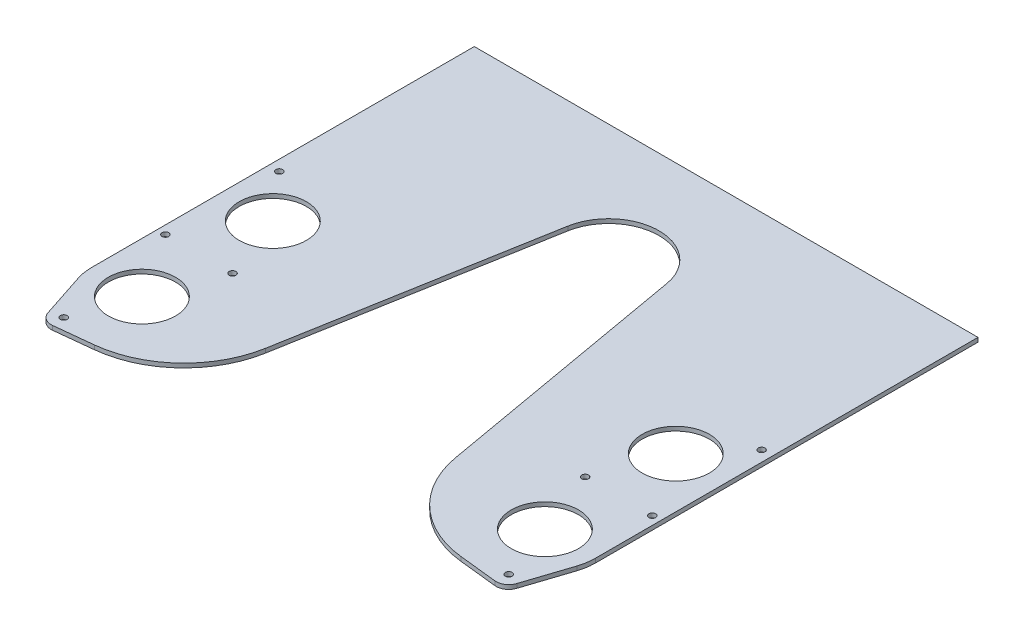
SolidWorks part; units mm, degrees
material "PC High Viscosity"
ref_plane "Front" through (0, 0, 0) normal (0, 0, 1) x (1, 0, 0)
ref_plane "Top" through (0, 0, 0) normal (0, 1, 0) x (1, 0, 0)
ref_plane "Right" through (0, 0, 0) normal (1, 0, 0) x (0, 0, -1)
sketch "Sketch1" plane through (0, 0, 0) normal (0, 1, 0) x (1, 0, 0)
  line L0 (-190.5, 0) -> (-190.5, -69.0534) construction
  line L3 (0, 0) -> (-381, 0)
  line L4 (-381, -289.5092) -> (-381, 0)
  line L5 (-228.0212, -82.284) -> (-262.284, -276.5979)
  line L9 (-357.7595, -342.1937) -> (-329.2022, -339.1316)
  line L11 (-379.0949, -301.4062) -> (-367.8237, -335.6973)
  line L12 (-1.9051, -301.4062) -> (-13.1763, -335.6973)
  line L14 (-23.2405, -342.1937) -> (-51.7978, -339.1316)
  line L15 (-152.9788, -82.284) -> (-118.716, -276.5979)
  line L16 (0, -289.5092) -> (0, 0)
  arc A0 (-152.9788, -82.284) -> (-228.0212, -82.284) centre (-190.5, -88.9) ccw
  circle A1 centre (-342.9, -190.5) radius 25.4
  circle A3 centre (-372.8949, -155.575) radius 2.5527
  arc A8 (-367.8237, -335.6973) -> (-357.7595, -342.1937) centre (-358.775, -332.723) ccw
  circle A10 centre (-342.9, -289.5092) radius 25.4
  circle A11 centre (-342.9, -289.5092) radius 14.3129 construction
  arc A13 (-381, -289.5092) -> (-379.0949, -301.4062) centre (-342.9, -289.5092) ccw
  circle A14 centre (-358.775, -332.723) radius 2.5527
  circle A16 centre (-342.9, -289.5092) radius 38.1 construction
  circle A17 centre (-342.9, -190.5) radius 38.1 construction
  arc A21 (-329.2022, -339.1316) -> (-262.284, -276.5979) centre (-337.3263, -263.3659) ccw
  circle A22 centre (-374.65, -240.0046) radius 2.5527
  circle A23 centre (-323.85, -240.0046) radius 2.5527
  circle A24 centre (-57.15, -240.0046) radius 2.5527
  circle A25 centre (-6.35, -240.0046) radius 2.5527
  arc A26 (-51.7978, -339.1316) -> (-118.716, -276.5979) centre (-43.6737, -263.3659) cw
  circle A27 centre (-22.225, -332.723) radius 2.5527
  arc A28 (0, -289.5092) -> (-1.9051, -301.4062) centre (-38.1, -289.5092) cw
  circle A29 centre (-38.1, -289.5092) radius 25.4
  arc A30 (-13.1763, -335.6973) -> (-23.2405, -342.1937) centre (-22.225, -332.723) cw
  circle A31 centre (-8.1051, -155.575) radius 2.5527
  circle A32 centre (-38.1, -190.5) radius 25.4
  circle A33 centre (-374.65, -240.0046) radius 2.5527 construction
  circle A34 centre (-323.85, -240.0046) radius 2.5527 construction
  point P20 (-363.9119, -204.8733)
  point P22 (-344.9278, -165.1)
  point P55 (-127.9647, -202.1994)
  dimension "D3" = 190.5
  dimension "D4" = 38.1
  dimension "D5" = 50.8
  dimension "D6" = 5.1054
  dimension "D7" = 25.4
  dimension "D8" = 9.525
  dimension "D9" = 50.8
  dimension "D10" = 76.2
  dimension "D11" = 20
  dimension "D12" = 38.1
  dimension "D13" = 76.2
  dimension "D1" = 381
extrude "Boss-Extrude1" add sketch "Sketch1" along normal blind 3.175
